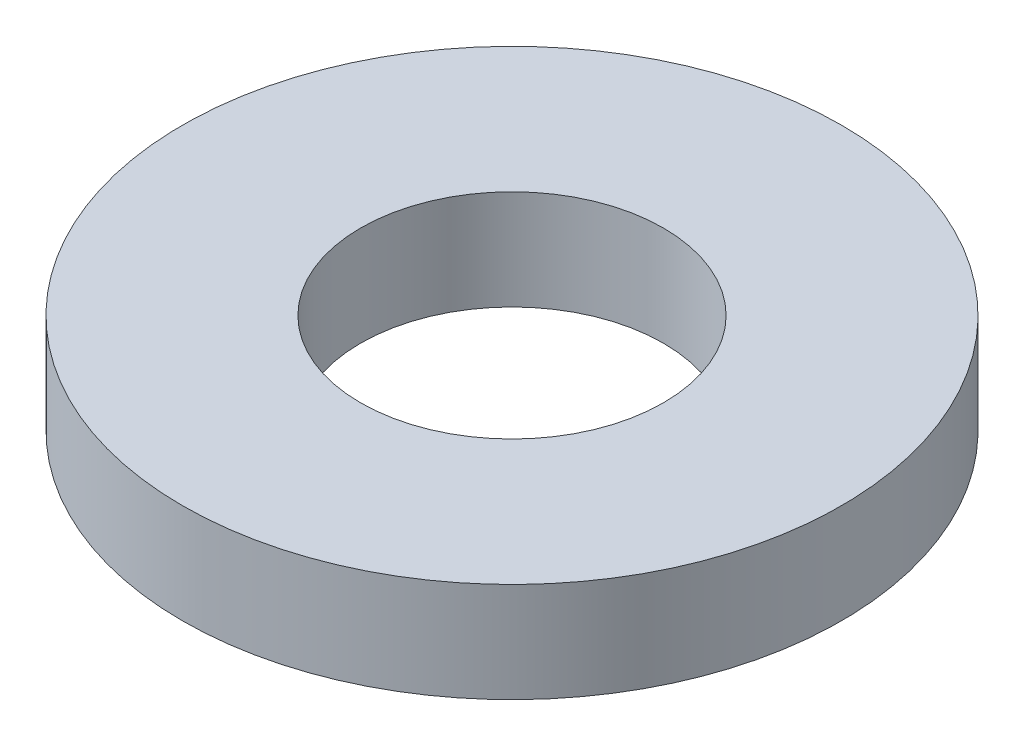
SolidWorks part; units mm, degrees
ref_plane "Front Plane" through (0, 0, 0) normal (0, 0, 1) x (1, 0, 0)
ref_plane "Top Plane" through (0, 0, 0) normal (0, 1, 0) x (1, 0, 0)
ref_plane "Right Plane" through (0, 0, 0) normal (1, 0, 0) x (0, 0, -1)
sketch "Sketch1" plane through (0, 0, 0) normal (0, 1, 0) x (1, 0, 0)
  circle A0 centre (0, 0) radius 92.5
  dimension "FLANGE_OD" = 185
extrude "Boss-Extrude1" add sketch "Sketch1" along normal blind 28
sketch "Sketch2" plane through (0, 0, 0) normal (0, 1, 0) x (1, 0, 0)
  circle A0 centre (0, 0) radius 42.5
  dimension "BORE_D" = 85
extrude "Cut-Extrude1" cut sketch "Sketch2" along normal through all
sketch "Sketch3" plane through (0, 28, 0) normal (0, 1, 0) x (1, 0, 0)
  circle A0 centre (0, 0) radius 32.3299 construction
  circle A1 centre (-32.3299, 0) radius 8.2963
  dimension "BOLT_D" = 16.5926
  dimension "BOLT_PCD" = 64.6598
extrude "Cut-Extrude2" cut sketch "Sketch3" against normal blind 20.3722 rebuild error yes
pattern_circular "CirPattern1" count 3 over 360 rebuild error yes
